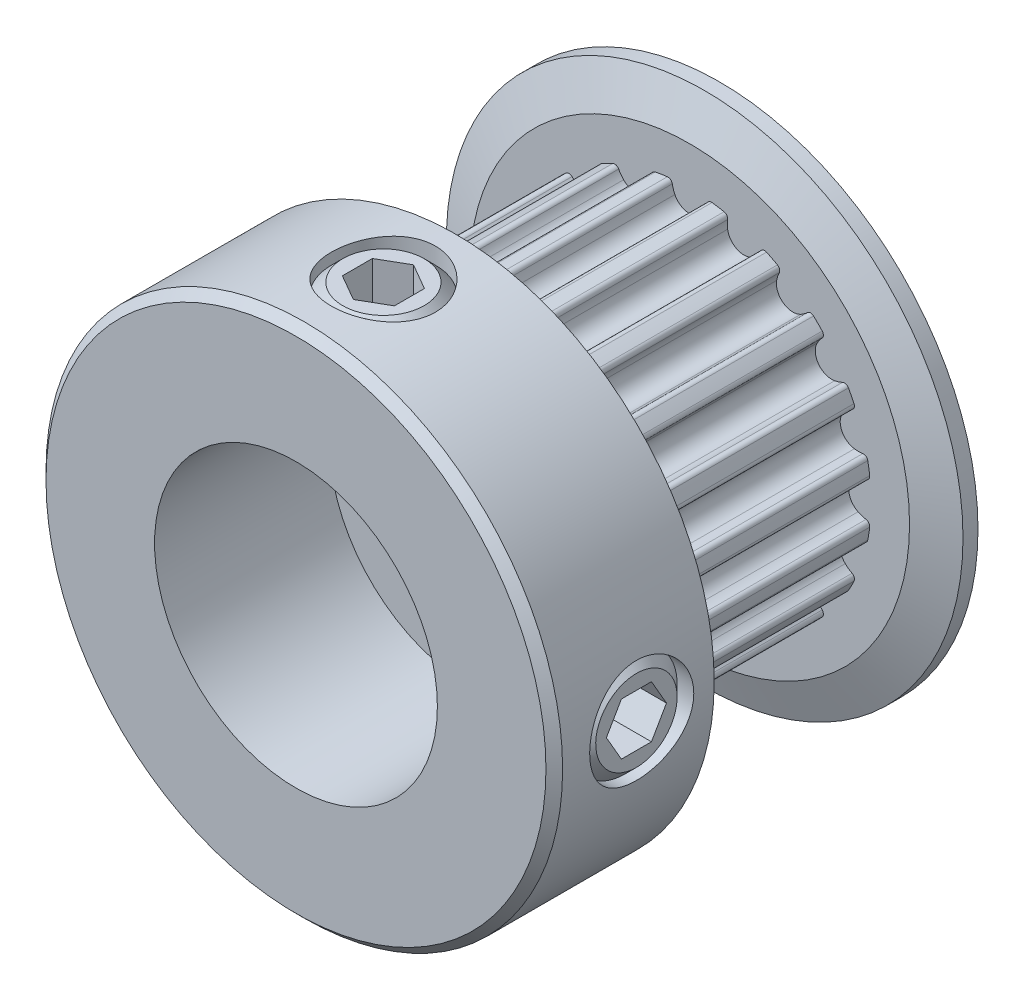
SolidWorks part; units mm, degrees
ref_plane "Front Plane" through (0, 0, 0) normal (0, 0, 1) x (1, 0, 0)
ref_plane "Top Plane" through (0, 0, 0) normal (0, 1, 0) x (1, 0, 0)
ref_plane "Right Plane" through (0, 0, 0) normal (1, 0, 0) x (0, 0, -1)
sketch "Sketch1" plane through (0, 0, 0) normal (0, 0, 1) x (1, 0, 0)
  line L1 (-1.7499, 5.3585) -> (1.7499, 5.3585) construction
  line L4 (0, 0) -> (0, 5.3585) construction
  line L5 (0, 5.3585) -> (0, 11.2144) construction
  line L6 (0, 6.3625) -> (1.9751, 6.0482) construction
  line L7 (1.9751, 6.0482) -> (2.6648, 5.8229) construction
  line L8 (1.9751, 6.0482) -> (1.7499, 5.3585) construction
  line L9 (-1.9751, 6.0482) -> (-1.7499, 5.3585) construction
  line L10 (-1.8963, 5.8067) -> (-2.841, 8.6995)
  line L11 (-2.841, 8.6995) -> (2.841, 8.6995)
  line L12 (2.841, 8.6995) -> (1.8963, 5.8067)
  circle A0 centre (0, 0) radius 6.3625 construction
  circle A1 centre (0, 0) radius 8.6995 construction
  circle A2 centre (0, 0) radius 6.1085 construction
  arc A3 (-0.4989, 5.6703) -> (0.4989, 5.6703) centre (0, 5.9135) ccw
  arc A4 (-0.4989, 5.6703) -> (-0.5855, 5.9387) centre (0.4, 6.1085) cw
  arc A5 (-1.8963, 5.8067) -> (-0.7518, 6.0621) centre (0, 0) cw
  arc A6 (-0.5855, 5.9387) -> (-0.7518, 6.0621) centre (-0.7333, 5.9132) ccw
  arc A7 (1.8963, 5.8067) -> (0.7518, 6.0621) centre (0, 0) ccw
  arc A8 (0.5855, 5.9387) -> (0.7518, 6.0621) centre (0.7333, 5.9132) cw
  arc A9 (0.4989, 5.6703) -> (0.5855, 5.9387) centre (-0.4, 6.1085) ccw
  point P6 (0, 20.9083)
  point P11 (0, 6.3625)
  point P13 (0, 8.6995)
  point P14 (0, 6.1085)
  dimension "D1" = 9.6939
  dimension "D2" = 4.8519
sketch "Sketch2" plane through (0, 0, 0) normal (1, 0, 0) x (0, 0, -1)
  line L0 (-7.135, 3.175) -> (7.135, 3.175)
  line L1 (-7.135, 3.175) -> (-7.135, 8.6995)
  line L2 (-1.75, 8.6995) -> (-7.135, 8.6995)
  line L3 (-2.255, 3.175) -> (-2.255, 8.6995) construction
  line L4 (-2.255, 8.6995) -> (-1.245, 8.6995) construction
  line L5 (-1.245, 8.6995) -> (-1.245, 6.1085) construction
  line L6 (-1.245, 6.1085) -> (6.125, 6.1085)
  line L7 (6.125, 6.1085) -> (6.125, 8.6995) construction
  line L8 (6.125, 8.6995) -> (7.135, 8.6995) construction
  line L9 (7.135, 8.6995) -> (7.135, 3.175)
  line L10 (-7.135, 0) -> (7.135, 0) construction
  line L11 (6.63, 8.6995) -> (6.125, 7.404)
  line L12 (-1.245, 7.404) -> (-1.75, 8.6995)
  line L14 (-1.245, 7.404) -> (-1.245, 6.1085)
  line L15 (6.125, 6.1085) -> (6.125, 7.404)
  line L16 (6.63, 8.6995) -> (7.135, 8.6995)
  arc A0 (-1.245, 7.404) -> (-1.75, 8.6995) centre (-3.1592, 7.404) ccw construction
  arc A1 (6.125, 7.404) -> (6.63, 8.6995) centre (8.0392, 7.404) cw construction
  point P12 (-1.245, 7.404)
  point P14 (-1.75, 8.6995)
  point P20 (6.125, 7.404)
  point P21 (6.63, 8.6995)
  point P25 (6.125, 0)
  point P26 (-1.245, 0)
  dimension "OA" = 14.27
  dimension "Bore" = 6.35
  dimension "Outside Width" = 8.38
  dimension "Inside Width" = 7.37
revolve "Revolve1" add sketch "Sketch2" angle 360 mid plane about L10
sketch "Sketch3" plane through (0, 0, 0) normal (0, 0, 1) x (1, 0, 0)
  line L6 (2.841, 8.6995) -> (-2.841, 8.6995)
  line L7 (1.8963, 5.8067) -> (2.841, 8.6995)
  line L8 (-2.841, 8.6995) -> (-1.8963, 5.8067)
  line L9 (2.841, 8.6995) -> (-2.841, 8.6995)
  line L10 (1.8963, 5.8067) -> (2.841, 8.6995)
  line L11 (-2.841, 8.6995) -> (-1.8963, 5.8067)
  arc A8 (1.8963, 5.8067) -> (0.7518, 6.0621) centre (0, 0) ccw
  arc A9 (0.7518, 6.0621) -> (0.5855, 5.9387) centre (0.7333, 5.9132) ccw
  arc A10 (0.4989, 5.6703) -> (0.5855, 5.9387) centre (-0.4, 6.1085) ccw
  arc A11 (-0.4989, 5.6703) -> (0.4989, 5.6703) centre (0, 5.9135) ccw
  arc A12 (-0.5855, 5.9387) -> (-0.4989, 5.6703) centre (0.4, 6.1085) ccw
  arc A13 (-0.5855, 5.9387) -> (-0.7518, 6.0621) centre (-0.7333, 5.9132) ccw
  arc A14 (-0.7518, 6.0621) -> (-1.8963, 5.8067) centre (0, 0) ccw
  arc A15 (1.8963, 5.8067) -> (0.7518, 6.0621) centre (0, 0) ccw
  arc A16 (0.7518, 6.0621) -> (0.5855, 5.9387) centre (0.7333, 5.9132) ccw
  arc A17 (0.4989, 5.6703) -> (0.5855, 5.9387) centre (-0.4, 6.1085) ccw
  arc A18 (-0.4989, 5.6703) -> (0.4989, 5.6703) centre (0, 5.9135) ccw
  arc A19 (-0.5855, 5.9387) -> (-0.4989, 5.6703) centre (0.4, 6.1085) ccw
  arc A20 (-0.5855, 5.9387) -> (-0.7518, 6.0621) centre (-0.7333, 5.9132) ccw
  arc A21 (-0.7518, 6.0621) -> (-1.8963, 5.8067) centre (0, 0) ccw
  dimension "D1" = 0
extrude "Cut-Extrude1" cut sketch "Sketch3" against normal up to vertex (6.125 mm away) from vertex up to point (0, 6.1085, -6.125) starting at point (0, 6.1085, 1.245)
pattern_circular "CirPattern1" count 20 over 360 about axis through (0, 0, 7.135) along (0, 0, 1) of "Cut-Extrude1"
sketch "Sketch4" plane through (0, 0, 0) normal (1, 0, 0) x (0, -1, 0)
  line L0 (0, -1.245) -> (0, -7.135) construction
  line L1 (-3.175, -7.135) -> (3.175, -7.135) construction
  line L2 (7.404, -1.245) -> (-7.404, -1.245) construction
  circle A0 centre (0, -4.19) radius 1.7526
extrude "Cut-Extrude2" cut sketch "Sketch4" along normal through all
ref_plane "Plane1" through (0, 0, 4.19) normal (0, 0, 1) x (1, 0, 0)
sketch "Sketch5" plane through (0, 0, 4.19) normal (0, 0, 1) x (1, 0, 0)
  line L0 (0, 0) -> (0, 8.6995) construction
  line L1 (3.175, -1.3716) -> (3.175, 0)
  line L2 (3.556, -1.7526) -> (8.1401, -1.7526)
  line L3 (3.175, 0) -> (8.6995, 0) construction
  line L4 (3.175, 0) -> (8.5211, 0)
  line L5 (8.5211, 0) -> (8.5211, -1.3716)
  line L6 (3.556, -1.7526) -> (3.175, -1.3716)
  line L7 (8.5211, -1.3716) -> (8.1401, -1.7526)
  circle A0 centre (0, 0) radius 8.6995 construction
  circle A1 centre (0, 0) radius 3.175 construction
  point P2 (3.175, -1.7526)
  point P11 (8.5211, -1.7526)
revolve "Revolve2" add sketch "Sketch5" angle 360 mid plane about L4
sketch "Sketch6" plane through (8.5211, 5.3841, 0) normal (-1, 0, 0) x (0, -1, 0)
  line L1 (5.3841, 5.2019) -> (4.5078, 4.6959)
  line L2 (4.5078, 4.6959) -> (4.5078, 3.6841)
  line L3 (4.5078, 3.6841) -> (5.3841, 3.1781)
  line L4 (5.3841, 3.1781) -> (6.2604, 3.6841)
  line L5 (6.2604, 3.6841) -> (6.2604, 4.6959)
  line L6 (6.2604, 4.6959) -> (5.3841, 5.2019)
  circle A0 centre (5.3841, 4.19) radius 0.8763 construction
  dimension "D1" = 1.7526
extrude "Cut-Extrude3" cut sketch "Sketch6" along normal blind 1.3144
pattern_circular "CirPattern3" count 2 over 90 about axis through (0, 0, 7.135) along (0, 0, 1) of "Cut-Extrude2", "Revolve2", "Cut-Extrude3"
chamfer "Chamfer1" distance 0.2807 angle 45 2 edges at (3.175, 0, 7.135) (8.6995, 0, 7.135)
ref_axis "Center Axis 1" through (0, 0, -7.135) along (0, 0, 1)
ref_plane "Contact Plane 1" through (0, 0, 7.135) normal (0, 0, 1) x (1, 0, 0)
ref_plane "Contact Plane 2" through (0, 0, -7.135) normal (0, 0, -1) x (-1, 0, 0)
sketch "Sketch7" plane through (0, 0, 7.135) normal (0, 0, 1) x (1, 0, 0)
  circle A0 centre (0, 0) radius 4.7625
  circle A1 centre (0, 0) radius 3.4558 construction
  dimension "D1" = 9.525
extrude "Cut-Extrude4" cut sketch "Sketch7" against normal up to surface (5.89 mm away) up to face at (0, 0, 1.245)
equation "\"D2@Sketch1\"= \"D1@Sketch1\" / 2"
equation "\"D1@Sketch6\" = \"Set Screw@Sketch4\" / 2"
equation "\"D1@Cut-Extrude3\" = \"D1@Sketch6\"*.75"
